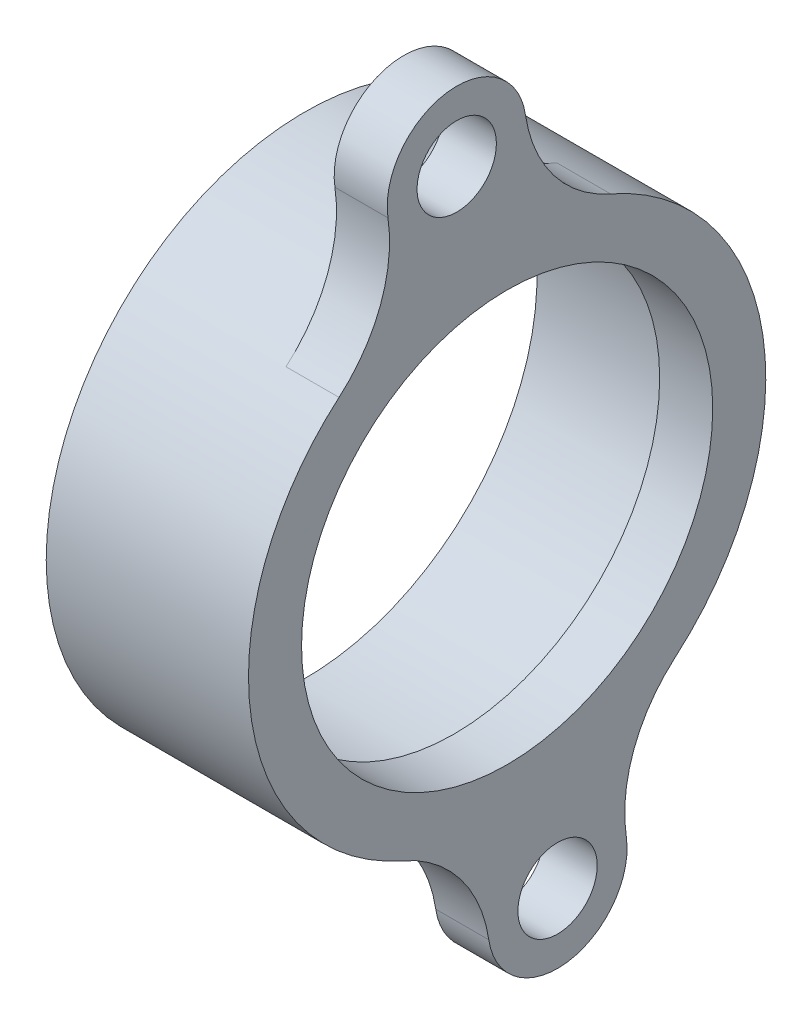
SolidWorks part; units mm, degrees
ref_plane "Front Plane" through (0, 0, 0) normal (0, 0, 1) x (1, 0, 0)
ref_plane "Top Plane" through (0, 0, 0) normal (0, 1, 0) x (1, 0, 0)
ref_plane "Right Plane" through (0, 0, 0) normal (1, 0, 0) x (0, 0, -1)
sketch "Sketch1" plane through (0, 0, 0) normal (0, 0, 1) x (1, 0, 0)
  line L0 (30.9563, 12.3825) -> (38.1, 12.3825)
  line L1 (38.1, 12.3825) -> (38.1, 11.1125)
  line L2 (38.1, 11.1125) -> (30.9563, 11.1125)
  line L4 (30.9563, 11.1125) -> (30.9563, 12.3825)
  line L5 (0, 0) -> (40.0174, 0) construction
  dimension "D1" = 1.27
  dimension "D2" = 7.1437
revolve "Revolve1" add sketch "Sketch1" angle 360 about L5
sketch "Sketch2" plane through (38.1, 0, 0) normal (1, 0, 0) x (0, 0, -1)
  line L0 (3.7, -24.7915) -> (-3.7, 24.7915) construction
  line L1 (-5.7046, 15.681) -> (0.8773, 16.6633) construction
  line L2 (-11.5595, -1.7252) -> (11.5595, 1.7252) construction
  line L4 (-4.094, 11.9086) -> (0.4385, 12.5851) construction
  line L5 (0.4385, 12.5851) -> (2.1189, 16.8486) construction
  line L6 (2.1189, 16.8486) -> (-0.7332, 20.4356) construction
  line L7 (-0.7332, 20.4356) -> (-5.2657, 19.7592) construction
  line L8 (-5.2657, 19.7592) -> (-6.9461, 15.4957) construction
  line L9 (-6.9461, 15.4957) -> (-4.094, 11.9086) construction
  arc A0 (-8.0474, 9.4109) -> (-4.9489, -11.3505) centre (0, 0) ccw
  circle A1 centre (0, 0) radius 12.3825 construction
  arc A7 (0.8773, 16.6633) -> (-5.7046, 15.681) centre (-2.4136, 16.1721) ccw
  arc A8 (-8.0474, 9.4109) -> (-5.7046, 15.681) centre (-12.5371, 14.6613) ccw
  arc A9 (0.8773, 16.6633) -> (4.9489, 11.3505) centre (7.7099, 17.683) ccw
  circle A10 centre (0, 0) radius 9.8425
  circle A11 centre (0, 0) radius 11.1125 construction
  arc A12 (5.7046, -15.681) -> (8.0474, -9.4109) centre (12.5371, -14.6613) cw
  arc A14 (5.7046, -15.681) -> (-0.8773, -16.6633) centre (2.4136, -16.1721) cw
  arc A15 (-4.9489, -11.3505) -> (-0.8773, -16.6633) centre (-7.7099, -17.683) cw
  arc A16 (8.0474, -9.4109) -> (4.9489, 11.3505) centre (0, 0) ccw
  circle A17 centre (-2.4136, 16.1721) radius 3.9688 construction
  arc A18 (1.509, 20.9354) -> (-7.5561, 19.5825) centre (-3.0235, 20.259) ccw construction
  arc A19 (-1.509, -20.9354) -> (7.5561, -19.5825) centre (3.0235, -20.259) ccw construction
  dimension "D1" = 1.27
  dimension "D2" = 3.3274
  dimension "D3" = 7.9375
extrude "Boss-Extrude1" add sketch "Sketch2" along normal blind 2.54
hole_wizard "#6 Clearance Hole1" positions "Sketch3" profile "Sketch5" hole size "#6" standard "ANSI Inch" end condition up to next
sketch "Sketch3" plane through (40.64, 0, 0) normal (1, 0, 0) x (0, 0, -1)
  point P0 (-2.4136, 16.1721)
  point P3 (2.4136, -16.1721)
sketch "Sketch5" plane through (40.64, 16.1721, 2.4136) normal (0, 1, 0) x (0, 0, -1)
  line L0 (0, 0) -> (0, 2.54)
  line L1 (0, 2.54) -> (1.8986, 2.54)
  line L2 (1.8986, 2.54) -> (1.8986, 0)
  line L5 (1.8986, 0) -> (0, 0)
  line L11 (0, -6.35) -> (0, 107.95) construction
  dimension "Thru Hole Dia." = 3.7973
  dimension "Thru Hole Depth" = 2.54
